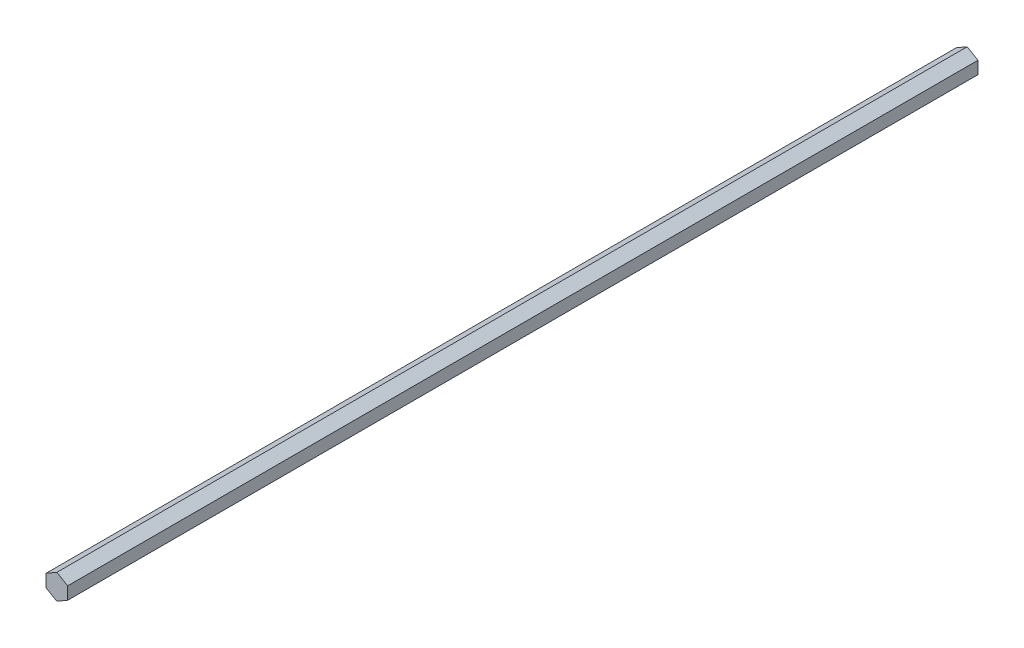
SolidWorks part; units mm, degrees
ref_plane "Front Plane" through (0, 0, 0) normal (0, 0, 1) x (1, 0, 0)
ref_plane "Top Plane" through (0, 0, 0) normal (0, 1, 0) x (1, 0, 0)
ref_plane "Right Plane" through (0, 0, 0) normal (1, 0, 0) x (0, 0, -1)
sketch "Sketch1" plane through (0, 0, 0) normal (0, 0, 1) x (1, 0, 0)
  line L0 (-6.35, 0) -> (6.35, 0) construction
  line L9 (0, 7.3323) -> (-6.35, 3.6662) construction
  line L10 (-6.35, 3.6662) -> (-6.35, -3.6662) construction
  line L11 (-6.35, -3.6662) -> (0, -7.3323) construction
  line L12 (0, -7.3323) -> (6.35, -3.6662) construction
  line L13 (6.35, -3.6662) -> (6.35, 3.6662) construction
  line L14 (6.35, 3.6662) -> (0, 7.3323) construction
  circle A3 centre (0, 0) radius 6.35 construction
  point P4 (0, 0)
  dimension "Width" = 12.7
sketch "Sketch2" plane through (0, 0, 0) normal (1, 0, 0) x (0, 0, -1)
  line L0 (266.7, 7.3323) -> (-266.7, 7.3323) construction
  point P3 (-252.095, 7.3323)
  point P4 (0, 7.3323)
  point P5 (252.095, 7.3323)
  dimension "Length" = 533.4
  dimension "D1" = 14.605
  dimension "D2" = 14.605
sketch "Sketch3" plane through (0, 0, 0) normal (0, 0, 1) x (1, 0, 0)
  line L1 (0, 7.3323) -> (6.35, 3.6662)
  line L2 (6.35, 3.6662) -> (6.35, -3.6662)
  line L3 (6.35, -3.6662) -> (0, -7.3323)
  line L4 (0, -7.3323) -> (-6.35, -3.6662)
  line L5 (-6.35, -3.6662) -> (-6.35, 3.6662)
  line L6 (-6.35, 3.6662) -> (0, 7.3323)
extrude "Boss-Extrude1" add sketch "Sketch3" along normal mid plane 533.4
equation "\"D1@Boss-Extrude1\" = \"Length@Sketch2\""
equation "\"D1@Sketch2\" = \"Width@Sketch1\" * 1.15"
equation "\"D2@Sketch2\"=\"D1@Sketch2\""
